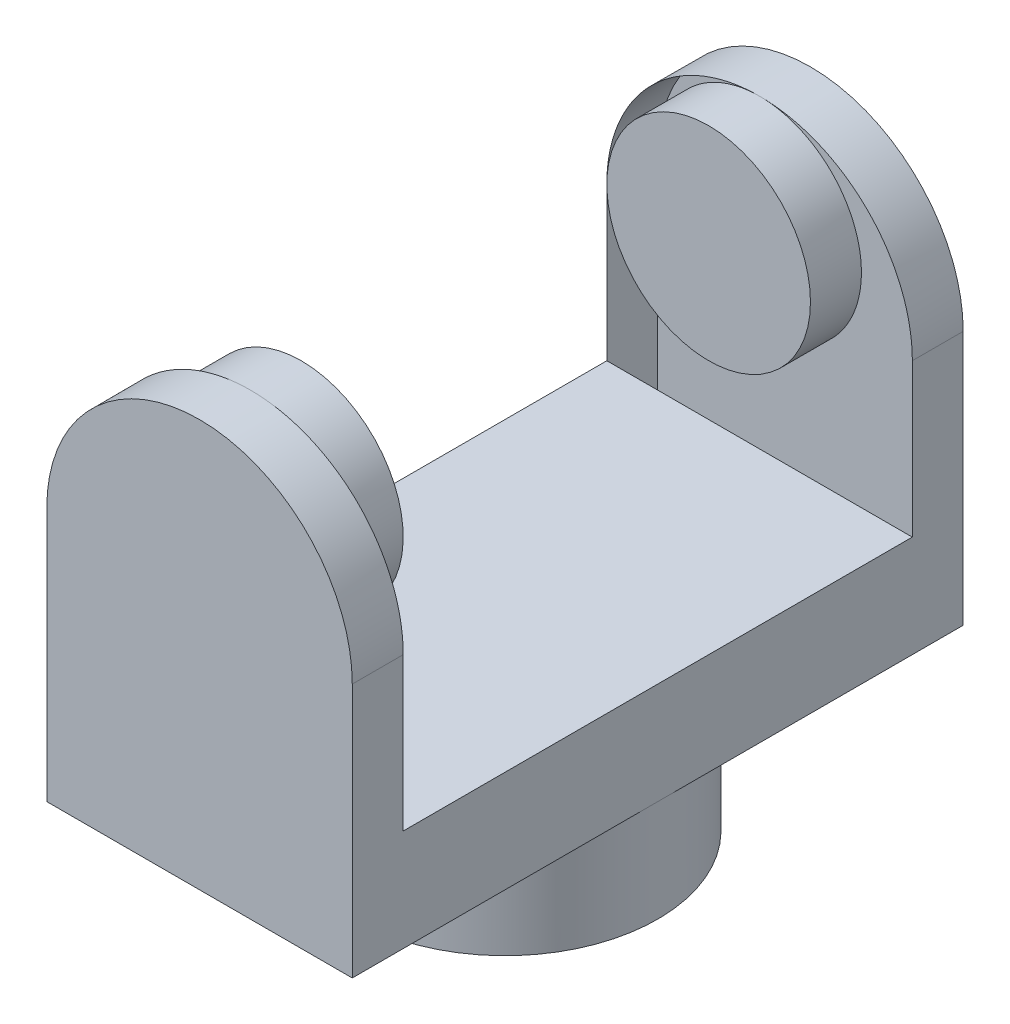
SolidWorks part; units mm, degrees
ref_plane "Plano frontal" through (0, 0, 0) normal (0, 0, 1) x (1, 0, 0)
ref_plane "Plano superior" through (0, 0, 0) normal (0, 1, 0) x (1, 0, 0)
ref_plane "Plano direito" through (0, 0, 0) normal (1, 0, 0) x (0, 0, -1)
sketch "Esboço1" plane through (0, 0, 0) normal (0, 1, 0) x (1, 0, 0)
  circle A0 centre (0, 0) radius 1.5
  dimension "D1" = 3
extrude "Ressalto-extrusão1" add sketch "Esboço1" against normal blind 1
sketch "Esboço3" plane through (0, 0, 0) normal (0, 1, 0) x (1, 0, 0)
  line L1 (-1.5, -3) -> (1.5, -3)
  line L2 (-1.5, -3) -> (-1.5, 3)
  line L3 (-1.5, 3) -> (1.5, 3)
  line L4 (1.5, -3) -> (1.5, 3)
  line L5 (-1.5, -3) -> (1.5, 3) construction
  line L6 (-1.5, 3) -> (1.5, -3) construction
  circle A0 centre (0, 0) radius 1.5 construction
  point P0 (0, 0)
  dimension "D1" = 6
extrude "Ressalto-extrusão2" add sketch "Esboço3" along normal blind 1
sketch "Esboço4" plane through (0, 0, 3) normal (0, 0, 1) x (1, 0, 0)
  line L0 (-1.5, 1) -> (1.5, 1) construction
  circle A0 centre (0, 2.5) radius 1.5
  dimension "D1" = 3
extrude "Ressalto-extrusão3" add sketch "Esboço4" against normal blind 0.5 separate body contours A0
sketch "Esboço5" plane through (0, 0, 2.5) normal (0, 0, -1) x (-1, 0, 0)
  circle A0 centre (0, 3) radius 1
  circle A1 centre (0, 2.5) radius 1.5 construction
  dimension "D1" = 2
extrude "Ressalto-extrusão4" add sketch "Esboço5" along normal blind 0.5
sketch "Esboço6" plane through (0, 0, 2.5) normal (0, 0, -1) x (-1, 0, 0)
  line L0 (-1.5, 2.5) -> (-1.5, 1)
  line L1 (-1.5, 1) -> (1.5, 1)
  line L2 (1.5, 1) -> (1.5, 2.5)
  circle A0 centre (0, 2.5) radius 1.5 construction
  arc A1 (-1.5, 2.5) -> (0, 1) centre (0, 2.5) ccw
  arc A2 (1.5, 2.5) -> (0, 1) centre (0, 2.5) cw
  circle M1 centre (0, 2.5) radius 1.5
extrude "Ressalto-extrusão5" add sketch "Esboço6" against normal blind 0.5 contours L0 L1 M1 | L1 L2 M1 region at (1.1649, 1.3351, 2.5) region at (-1.1649, 1.3351, 2.5)
sketch "Esboço7" plane through (0, 0, -3) normal (0, 0, -1) x (-1, 0, 0)
  circle A0 centre (0, 2.5) radius 1.5
  arc A1 (0, 4) -> (-1.5, 2.5) centre (0, 2.5) ccw construction
  dimension "D1" = 3
extrude "Ressalto-extrusão6" add sketch "Esboço7" against normal blind 0.5 separate body
sketch "Esboço8" plane through (0, 0, -2.5) normal (0, 0, 1) x (1, 0, 0)
  circle A0 centre (0, 3) radius 1
  arc A1 (1.5, 2.5) -> (-1.5, 2.5) centre (0, 2.5) ccw construction
  dimension "D1" = 2
extrude "Ressalto-extrusão7" add sketch "Esboço8" along normal blind 0.5
sketch "Esboço9" plane through (0, 0, -3) normal (0, 0, -1) x (-1, 0, 0)
  line L0 (-1.5, 2.5) -> (-1.5, 1)
  line L1 (-1.5, 1) -> (1.5, 1)
  line L2 (1.5, 1) -> (1.5, 2.5)
  line L3 (1.5, 1) -> (1.5, 2.5) construction
  circle A0 centre (0, 2.5) radius 1.5 construction
  arc A1 (-1.5, 2.5) -> (0, 1) centre (0, 2.5) ccw
  arc A2 (0, 1) -> (1.5, 2.5) centre (0, 2.5) ccw
  circle M1 centre (0, 2.5) radius 1.5
extrude "Ressalto-extrusão8" add sketch "Esboço9" against normal blind 0.5 contours L0 L1 M1 | L1 L2 M1 region at (1.1649, 1.3351, -3) region at (-1.1649, 1.3351, -3)
scale "Escala1" scale about origin uniform scaling yes scale factor 10
